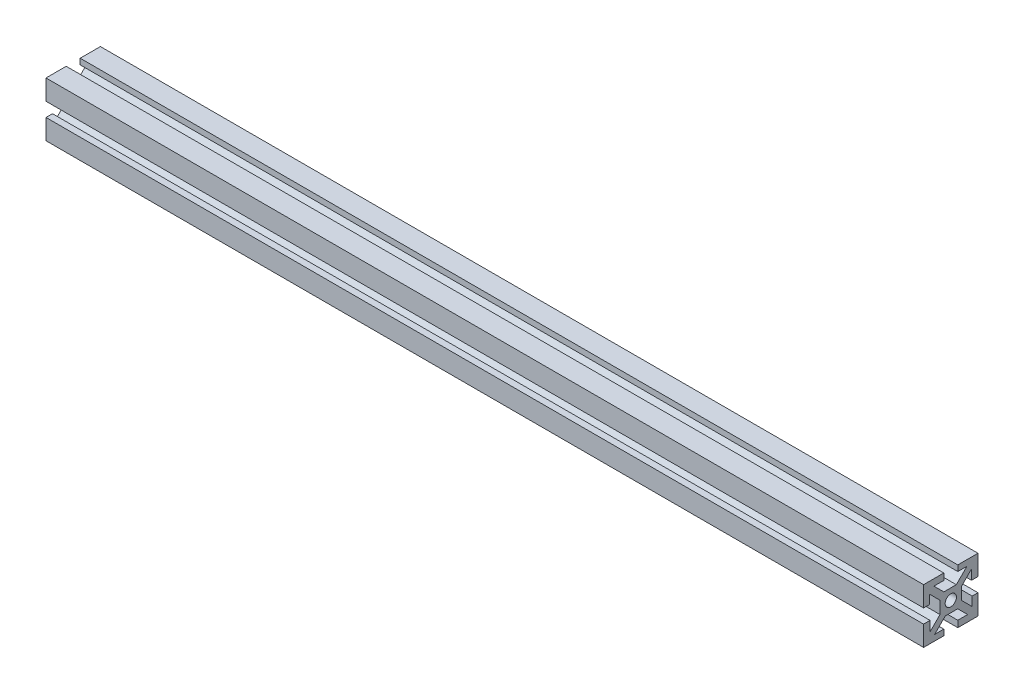
SolidWorks part; units mm, degrees
ref_plane "Front Plane" through (0, 0, 0) normal (0, 0, 1) x (1, 0, 0)
ref_plane "Top Plane" through (0, 0, 0) normal (0, 1, 0) x (1, 0, 0)
ref_plane "Right Plane" through (0, 0, 0) normal (1, 0, 0) x (0, 0, -1)
sketch "Sketch1" plane through (0, 0, 0) normal (1, 0, 0) x (0, 0, -1)
  line L0 (2.5534, 5) -> (7.4749, 9.9215)
  line L1 (-5, 5) -> (5, 5)
  line L2 (-5, 5) -> (-5, -5)
  line L3 (-5, -5) -> (5, -5)
  line L4 (5, 5) -> (5, -5)
  line L5 (-5, 5) -> (5, -5) construction
  line L6 (-5, -5) -> (5, 5) construction
  line L7 (7.4749, 9.9215) -> (9.5962, 7.8001)
  line L8 (9.5962, 7.8001) -> (5, 3.2039)
  line L9 (5, 5) -> (13.6489, 13.6489) construction
  line L10 (7.4749, 9.9215) -> (3.24, 9.9215)
  line L11 (3.24, 9.9215) -> (3.24, 12.5962)
  line L12 (3.24, 12.5962) -> (12.5962, 12.5962)
  line L13 (9.5962, 7.8001) -> (9.5962, 3.24)
  line L14 (9.5962, 3.24) -> (12.5962, 3.24)
  line L15 (12.5962, 3.24) -> (12.5962, 12.5962)
  line L17 (0, 0) -> (0, 24.089) construction
  line L18 (0, 0) -> (23.75, 0) construction
  circle A0 centre (0, 0) radius 2.605
  point P0 (0, 0)
  dimension "D1" = 5.21
  dimension "D2" = 10
  dimension "D3" = 10
  dimension "D4" = 3
  dimension "D5" = 1.27
  dimension "D6" = 6.5
  dimension "D7" = 3.24
  dimension "D8" = 3.24
  dimension "D9" = 3
extrude "Boss-Extrude1" add sketch "Sketch1" along normal blind 406.4 contours L4 L1 L2 L3 A0 | L8 L7 L0 L1 L4 | L14 L15 L12 L11 L10 L7 L13 region at (0, 4.8586, -3.7767) region at (0, 6.7479, -6.3823) region at (0, 9.18, -9.3105)
ref_axis "Axis1" through (0, 0, 0) along (1, 0, 0)
pattern_circular "CirPattern1" count 4 over 360 about axis through (0, 0, 0) along (1, 0, 0) of "Boss-Extrude1"
